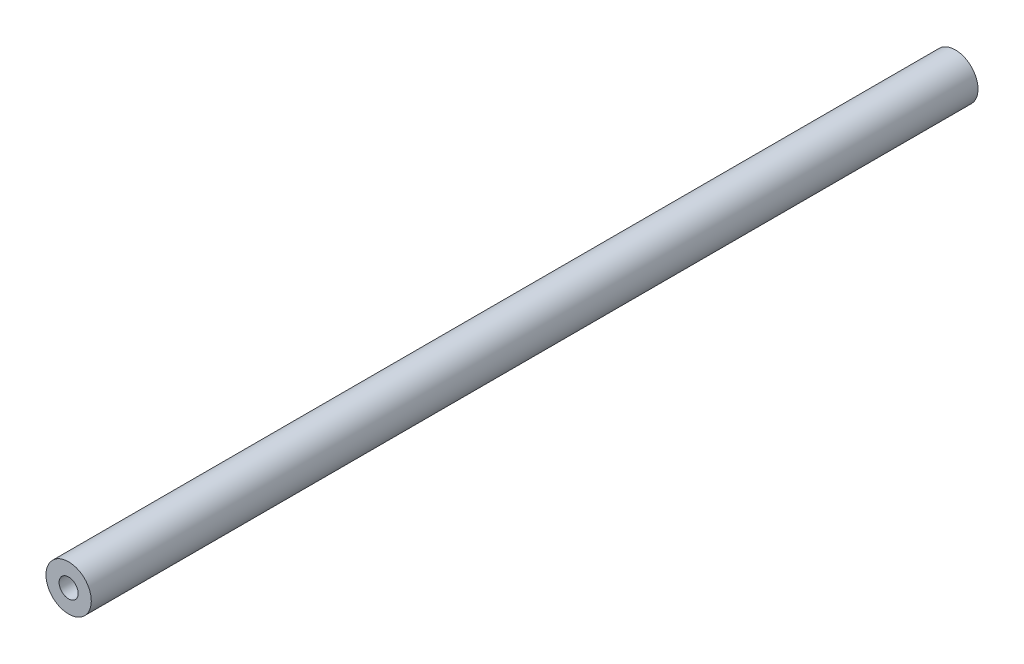
SolidWorks part; units mm, degrees
material "1060 Alloy"
ref_plane "Płaszczyzna przednia" through (0, 0, 0) normal (0, 0, 1) x (1, 0, 0)
ref_plane "Płaszczyzna górna" through (0, 0, 0) normal (0, 1, 0) x (1, 0, 0)
ref_plane "Płaszczyzna prawa" through (0, 0, 0) normal (1, 0, 0) x (0, 0, -1)
sketch "Sketch1" plane through (0, 0, 0) normal (0, 0, 1) x (1, 0, 0)
  circle A0 centre (0, 0) radius 5
  dimension "D1" = 10
extrude "Boss-Extrude1" add sketch "Sketch1" along normal blind 195.6
sketch "Szkic1" plane through (0, 0, 195.6) normal (0, 0, 1) x (1, 0, 0)
  point P0 (0, 0)
sketch "Szkic2" plane through (0, 0, 0) normal (0, 0, -1) x (-1, 0, 0)
  point P0 (0, 0)
sketch "Szkic5" plane through (0, 0, 0) normal (0, 0, -1) x (-1, 0, 0)
  point P0 (0, 0)
hole_wizard "Otwór gwintowany M52" positions "Szkic5" profile "Szkic6" tap size "M5" standard "DIN"
cosmetic thread "Oznaczenie gwintu2" parameters "D1"=20, "D2"=5
sketch "Szkic6" plane through (0, 0, 0) normal (1, 0, 0) x (0, 1, 0)
  line L0 (0, 0) -> (0, 21.2618)
  line L1 (0, 21.2618) -> (2.1, 20)
  line L2 (2.1, 20) -> (2.1, 0)
  line L5 (2.1, 0) -> (0, 0)
  line L10 (0, 21.2618) -> (-2.1, 20) construction
  line L11 (0, -6.35) -> (0, 107.95) construction
  dimension "Średnica wiertła gwintu" = 4.2
  dimension "Głębokość otworu gwintowanego" = 20
  dimension "Kąt wiertła" = 118
hole_wizard "Otwór gwintowany M51" positions "Szkic1" profile "Szkic7" tap size "M5" standard "DIN"
cosmetic thread "Oznaczenie gwintu1" parameters "D1"=20, "D2"=5
sketch "Szkic7" plane through (0, 0, 195.6) normal (1, 0, 0) x (0, -1, 0)
  line L0 (0, 0) -> (0, 21.2618)
  line L1 (0, 21.2618) -> (2.1, 20)
  line L2 (2.1, 20) -> (2.1, 0)
  line L5 (2.1, 0) -> (0, 0)
  line L10 (0, 21.2618) -> (-2.1, 20) construction
  line L11 (0, -6.35) -> (0, 107.95) construction
  dimension "Średnica wiertła gwintu" = 4.2
  dimension "Głębokość otworu gwintowanego" = 20
  dimension "Kąt wiertła" = 118
